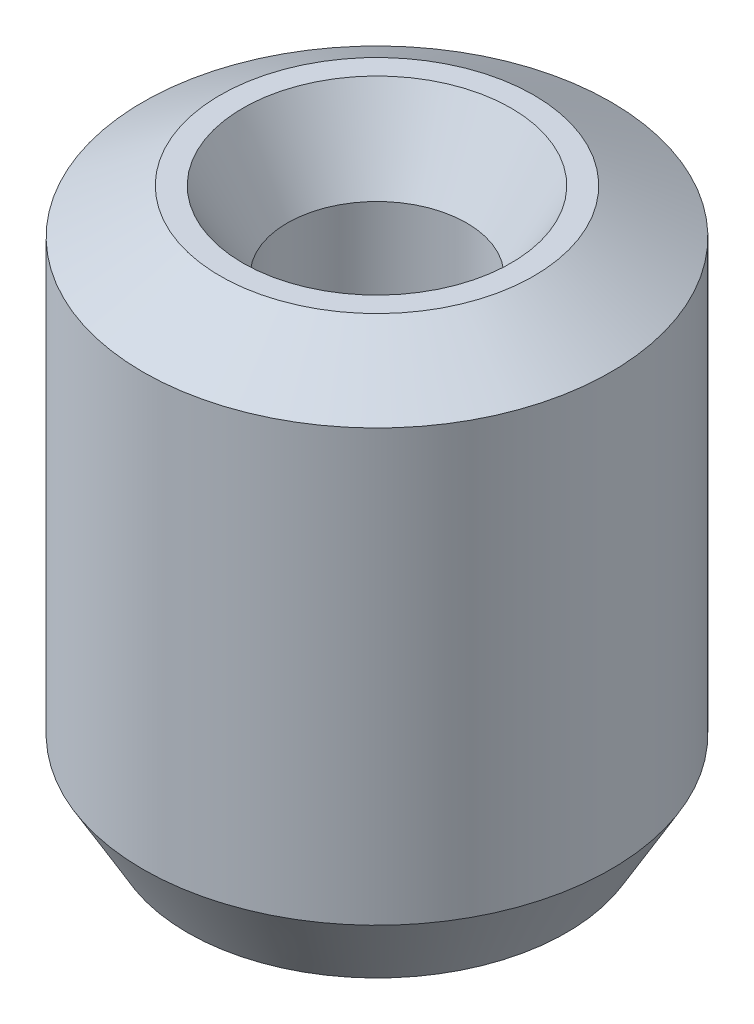
SolidWorks part; units mm, degrees
ref_plane "Front Plane" through (0, 0, 0) normal (0, 0, 1) x (1, 0, 0)
ref_plane "Top Plane" through (0, 0, 0) normal (0, 1, 0) x (1, 0, 0)
ref_plane "Right Plane" through (0, 0, 0) normal (1, 0, 0) x (0, 0, -1)
sketch "Sketch1" plane through (0, 0, 0) normal (0, 1, 0) x (1, 0, 0)
  circle A0 centre (0, 0) radius 5
  dimension "SLEEVE_OD" = 10
extrude "Boss-Extrude1" add sketch "Sketch1" along normal blind 11.8047
sketch "Sketch2" plane through (0, 0, 0) normal (0, 1, 0) x (1, 0, 0)
  circle A0 centre (0, 0) radius 1.9159
  dimension "BORE_D" = 3.8318
extrude "Cut-Extrude1" cut sketch "Sketch2" along normal through all
chamfer "Chamfer1" distance 0.952 angle 60 4 edges at (0, 11.8047, 1.9159) (0, 0, 1.9159) (0, 0, 5) (0, 11.8047, 5) first distance on face at (0, 11.8047, 1.9159) first distance on face at (0, 0, 1.9159) first distance on face at (0, 11.8047, 5)
